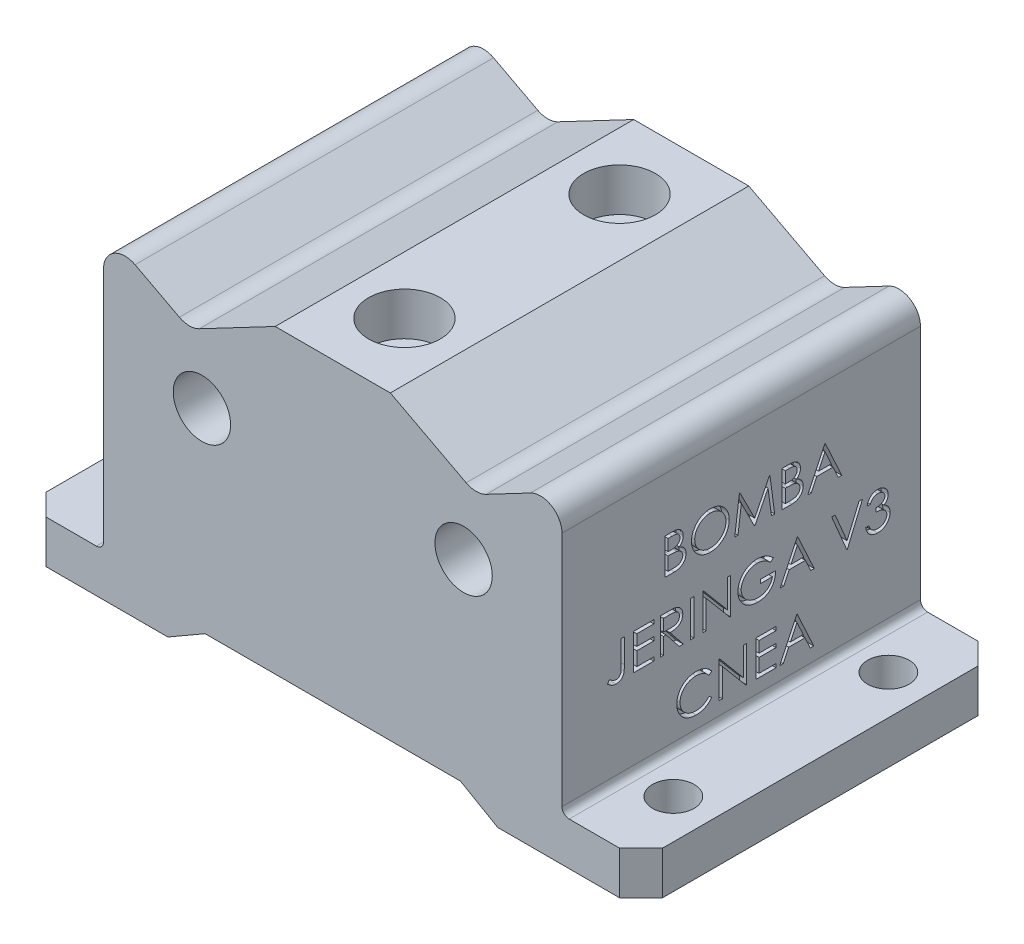
SolidWorks part; units mm, degrees
material "ABS PC"
ref_plane "Front Plane" through (0, 0, 0) normal (0, 0, 1) x (1, 0, 0)
ref_plane "Top Plane" through (0, 0, 0) normal (0, 1, 0) x (1, 0, 0)
ref_plane "Right Plane" through (0, 0, 0) normal (1, 0, 0) x (0, 0, -1)
sketch "Posicion Agujeros" plane through (0, 0, 0) normal (0, 0, 1) x (1, 0, 0)
  line L0 (-18.25, 30) -> (18.25, 30) construction
  line L3 (22, 20) -> (-22, 20) construction
  point P1 (0, 20)
  point P2 (0, 30)
  point P8 (22, 20)
  point P9 (-18.25, 30)
  point P10 (18.25, 30)
  point P18 (-22, 20)
  dimension "D1" = 36.5
  dimension "D2" = 44
  dimension "D3" = 20
  dimension "D4" = 30
  dimension "D5" = 10
sketch "Rodamiento" plane through (0, 0, 0) normal (0, 0, 1) x (1, 0, 0)
  line L0 (6.2877, 18.0537) -> (20.5788, 25.5754)
  line L1 (6.2877, 41.9463) -> (20.5788, 34.4246)
  line L2 (-6.2877, 18.0537) -> (-20.5788, 25.5754)
  line L3 (-20.5788, 34.4246) -> (-6.2877, 41.9463)
  arc A3 (20.5788, 25.5754) -> (20.5788, 34.4246) centre (18.25, 30) ccw
  arc A4 (-20.5788, 25.5754) -> (-20.5788, 34.4246) centre (-18.25, 30) cw
  arc A5 (6.2877, 18.0537) -> (-6.2877, 18.0537) centre (0, 30) cw
  arc A6 (6.2877, 41.9463) -> (-6.2877, 41.9463) centre (0, 30) ccw
  circle A7 centre (-18.25, 30) radius 2.5
  circle A8 centre (18.25, 30) radius 2.5
  arc A9 (-6.2877, 41.9463) -> (-6.2877, 18.0537) centre (0, 30) ccw construction
  dimension "D1" = 13.5
  dimension "D2" = 5
  dimension "D3" = 5
  dimension "D4" = 5
  dimension "D5" = 13.5
  dimension "D6" = 5
sketch "Croquis2" plane through (0, 0, 0) normal (0, 0, 1) x (1, 0, 0)
  line L2 (-43, 6) -> (-43, 0)
  line L3 (-43, 0) -> (-23, 0)
  line L4 (-23, 0) -> (-17.8038, 3)
  line L5 (-17.8038, 3) -> (0, 3)
  line L6 (0, 3) -> (0, 45)
  line L7 (0, 45) -> (-8.0292, 45)
  line L8 (-8.0292, 45) -> (-20, 38.6995)
  line L9 (-20, 38.6995) -> (-31.9708, 45)
  line L11 (-8.0292, 45) -> (-31.9708, 45) construction
  line L12 (-20, 45) -> (-20, 38.6995) construction
  line L13 (-31.9708, 45) -> (-31.9708, 6)
  line L14 (-20.5788, 34.4246) -> (-6.2877, 41.9463) construction
  line L15 (-31.9708, 6) -> (-43, 6)
  circle A0 centre (-20, 50) radius 10 construction
  circle A2 centre (-20, 50) radius 13.5134 construction
  dimension "D3" = 20
  dimension "D1" = 20
  dimension "D5" = 43
  dimension "D2" = 27.0267
  dimension "D4" = 20
  dimension "D6" = 3
  dimension "D7" = 20
  dimension "D8" = 30
  dimension "D9" = 3.5134
  dimension "D10" = 6
  dimension "D11" = 6.3005
  dimension "D12" = 124.482
  dimension "D13" = 45
extrude "Saliente-Extruir1" add sketch "Croquis2" along normal blind 25 and the other way blind 25
hole_wizard "Diámetro de taladro Ø8.6 (8.6)1" positions "Croquis20" profile "Croquis21" hole size "Ø8.6" standard "ISO"
sketch "Croquis20" plane through (0, 0, -25) normal (0, 0, -1) x (-1, 0, 0)
  point P0 (22, 20)
sketch "Croquis21" plane through (-22, 20, -25) normal (1, 0, 0) x (0, 1, 0)
  line L0 (0, 0) -> (0, 16.3)
  line L1 (0, 16.3) -> (4.3, 12)
  line L2 (4.3, 12) -> (4.3, 0)
  line L5 (4.3, 0) -> (0, 0)
  line L10 (0, 16.3) -> (-4.3, 12) construction
  line L11 (0, -6.35) -> (0, 107.95) construction
  dimension "Diámetro de taladro" = 8.6
  dimension "Profundidad de taladro" = 12
  dimension "Ángulo de perforador" = 90
fillet "Redondeo1" radius 3 2 edges at (-20, 38.6995, 0) (-31.9708, 45, 0)
chamfer "Chaflán1" distance 3 angle 45 2 edges at (-43, 3, -25) (-43, 3, 25)
fillet "Redondeo2" radius 1 1 edges at (-31.9708, 6, 0)
mirror "Simetría1" about plane through (0, 0, 0) normal (1, 0, 0) of "Chaflán1", "Redondeo2", "Diámetro de taladro Ø8.6 (8.6)1", "Saliente-Extruir1", "Redondeo1"
sketch "Croquis11" plane through (0, 0, -25) normal (0, 0, -1) x (-1, 0, 0)
  circle A0 centre (0, 30) radius 11
sketch "Croquis13" plane through (0, 0, 0) normal (0, 1, 0) x (1, 0, 0)
  line L1 (37.5, -15) -> (-37.5, -15) construction
  line L2 (37.5, -15) -> (37.5, 15) construction
  line L3 (37.5, 15) -> (-37.5, 15) construction
  line L4 (-37.5, -15) -> (-37.5, 15) construction
  line L5 (37.5, -15) -> (-37.5, 15) construction
  line L6 (37.5, 15) -> (-37.5, -15) construction
  point P5 (37.5, -15)
  point P6 (37.5, 15)
  point P7 (-37.5, 15)
  point P8 (-37.5, -15)
  dimension "D1" = 30
  dimension "D2" = 75
hole_wizard "Taladro de margen para M51" positions "Croquis14" profile "Croquis15" hole size "M5" standard "DIN" end condition through all
sketch "Croquis14" plane through (0, 45, 0) normal (0, -1, 0) x (-1, 0, 0)
  point P0 (37.5, 15)
sketch "Croquis15" plane through (-37.5, 45, -15) normal (1, 0, 0) x (0, 0, 1)
  line L0 (0, 0) -> (0, 45)
  line L1 (0, 45) -> (2.9, 45)
  line L2 (2.9, 45) -> (2.9, 0)
  line L5 (2.9, 0) -> (0, 0)
  line L11 (0, -6.35) -> (0, 107.95) construction
  dimension "Diámetro de taladro hasta el siguiente" = 5.8
  dimension "Profundidad de taladro hasta el siguiente" = 45
pattern_sketch "Matriz de croquis1" of "Taladro de margen para M51" driven by "Croquis13"
hole_wizard "Refrentado para tornillo con cabeza hueca de M42" positions "Croquis16" profile "Croquis17" counterbore size "M4" standard "DIN" end condition through all
sketch "Croquis16" plane through (0, 0, 25) normal (0, 0, -1) x (-1, 0, 0)
  point P0 (-18.25, 30)
  point P3 (18.25, 30)
sketch "Croquis17" plane through (18.25, 30, 25) normal (1, 0, 0) x (0, -1, 0)
  line L0 (0, 0) -> (0, 50)
  line L1 (0, 50) -> (2.4, 50)
  line L3 (2.4, 50) -> (2.4, 42)
  line L4 (2.4, 42) -> (4, 42)
  line L5 (4, 42) -> (4, 0)
  line L7 (4, 0) -> (0, 0)
  line L11 (0, -6.35) -> (0, 107.95) construction
  dimension "Diámetro de taladro hasta el siguiente" = 4.8
  dimension "Profundidad de taladro hasta el siguiente" = 50
  dimension "Diámetro de refrentado" = 8
  dimension "Profundidad de refrentado" = 42
sketch "Croquis25" plane through (0, 0, 0) normal (0, 1, 0) x (1, 0, 0)
  line L0 (0, 15) -> (0, -15) construction
  point P4 (0, 15)
  point P5 (0, -15)
  dimension "D1" = 30
hole_wizard "Refrentado para tornillo con cabeza hueca de M51" positions "Croquis26" profile "Croquis27" counterbore size "M5" standard "DIN" end condition through all
sketch "Croquis26" plane through (0, 3, 0) normal (0, -1, 0) x (-1, 0, 0)
  point P0 (0, 15)
  point P3 (0, -15)
sketch "Croquis27" plane through (0, 3, -15) normal (1, 0, 0) x (0, 0, -1)
  line L0 (0, 0) -> (0, 42)
  line L1 (0, 42) -> (2.75, 42)
  line L3 (2.75, 42) -> (2.75, 30)
  line L4 (2.75, 30) -> (5, 30)
  line L5 (5, 30) -> (5, 0)
  line L7 (5, 0) -> (0, 0)
  line L11 (0, -6.35) -> (0, 107.95) construction
  dimension "Diámetro de taladro hasta el siguiente" = 5.5
  dimension "Profundidad de taladro hasta el siguiente" = 42
  dimension "Diámetro de refrentado" = 10
  dimension "Profundidad de refrentado" = 30
hole_wizard "Refrentado para tornillo con cabeza hueca de M52" positions "Croquis33" profile "Croquis34" counterbore size "M5" standard "DIN" end condition through all
sketch "Croquis33" plane through (0, 45, 0) normal (0, 1, 0) x (1, 0, 0)
  point P0 (0, 15)
  point P3 (0, -15)
sketch "Croquis34" plane through (0, 45, -15) normal (1, 0, 0) x (0, 0, 1)
  line L0 (0, 0) -> (0, 45)
  line L1 (0, 45) -> (2.75, 45)
  line L3 (2.75, 45) -> (2.75, 6)
  line L4 (2.75, 6) -> (5, 6)
  line L5 (5, 6) -> (5, 0)
  line L7 (5, 0) -> (0, 0)
  line L11 (0, -6.35) -> (0, 107.95) construction
  dimension "Diámetro de taladro hasta el siguiente" = 5.5
  dimension "Profundidad de taladro hasta el siguiente" = 45
  dimension "Diámetro de refrentado" = 10
  dimension "Profundidad de refrentado" = 6
sketch "Croquis28" plane through (31.9708, 0, 0) normal (1, 0, 0) x (0, 0, -1)
  text T0 "    BOMBA \r\nJERINGA V3\r\n     CNEA" font "Century Gothic" height 5
extrude "Cortar-Extruir1" cut sketch "Croquis28" against normal blind 1
hole_wizard "Taladro1" positions "Croquis29" profile "Croquis30" legacy
sketch "Croquis29" plane through (-31.9708, 0, 0) normal (-1, 0, 0) x (0, 0, 1)
  line L0 (-18, 29.75) -> (-18, 20.25)
  point P0 (-18, 20.25)
  point P2 (-18, 29.75)
  point P10 (-18, 25)
  dimension "D1" = 9.5
  dimension "D2" = 18
  dimension "D3" = 25
sketch "Croquis30" plane through (-31.9708, 20.25, -18) normal (0, 1, 0) x (0, 0, 1)
  line L0 (0, 0) -> (0, 5)
  line L1 (0, 5) -> (2.05, 5)
  line L2 (2.05, 5) -> (2.05, 0)
  line L3 (2.05, 0) -> (0, 0)
  line L4 (0, 110) -> (0, -10) construction
  dimension "Diámetro" = 4.1
  dimension "Profundidad" = 5
